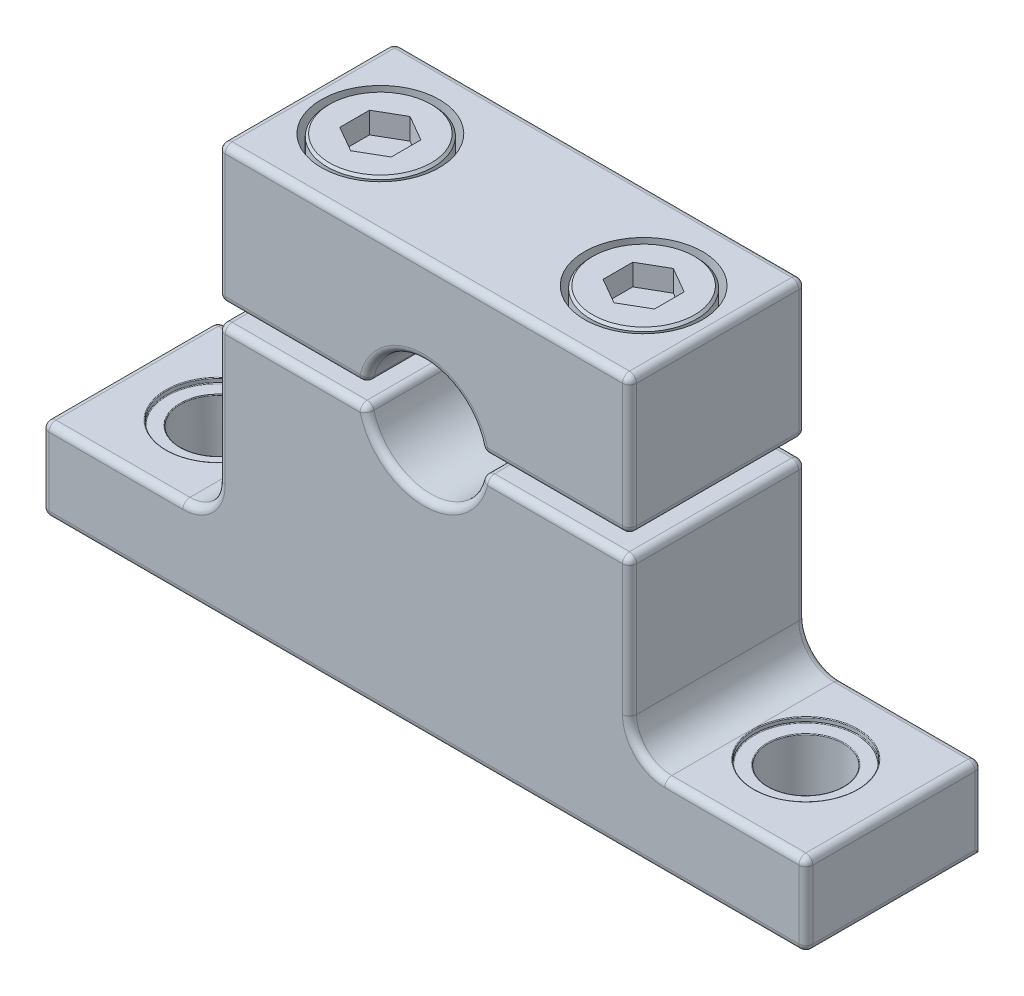
SolidWorks part; units mm, degrees
ref_plane "Front" through (0, 0, 0) normal (0, 0, 1) x (1, 0, 0)
ref_plane "Top" through (0, 0, 0) normal (0, 1, 0) x (1, 0, 0)
ref_plane "Right" through (0, 0, 0) normal (1, 0, 0) x (0, 0, -1)
sketch "Sketch1" plane through (0, 0, 0) normal (0, 0, 1) x (1, 0, 0)
  line L0 (0, 22.225) -> (0, 0) construction
  line L1 (-20.6375, 0) -> (20.6375, 0) construction
  line L2 (0, 0) -> (0, 14.2875) construction
  line L3 (-15.875, 0) -> (15.875, 0) construction
  line L4 (13.843, 0) -> (17.907, 0) construction
  line L5 (17.907, 0) -> (17.907, 1.27) construction
  line L6 (13.843, 0) -> (13.843, 1.27) construction
  line L7 (-13.843, 0) -> (-13.843, 1.27) construction
  line L8 (-17.907, 0) -> (-17.907, 1.27) construction
  line L9 (-13.843, 0) -> (-17.907, 0) construction
  line L10 (-11.1125, 14.2875) -> (11.1125, 14.2875) construction
  line L11 (-11.1125, 13.7795) -> (11.1125, 13.7795) construction
  line L12 (-11.1125, 14.7955) -> (11.1125, 14.7955) construction
  line L13 (13.462, 0) -> (13.462, 1.27) construction
  line L14 (18.288, 0) -> (18.288, 1.27) construction
  line L15 (-13.462, 0) -> (-13.462, 1.27) construction
  line L16 (-18.288, 0) -> (-18.288, 1.27) construction
  line L17 (-11.0713, 13.7795) -> (11.0713, 13.7795) construction
  line L18 (-11.0713, 14.7955) -> (11.0713, 14.7955) construction
  line L19 (-11.0713, 14.2875) -> (11.0713, 14.2875) construction
  line L20 (-20.6375, 0) -> (-20.6375, 4.445) construction
  line L21 (-20.6375, 4.445) -> (-11.1125, 4.445) construction
  line L22 (-11.1125, 13.7795) -> (-11.1125, 4.445) construction
  line L23 (-11.1125, 14.7955) -> (-11.1125, 22.225) construction
  line L24 (-11.1125, 22.225) -> (11.1125, 22.225) construction
  line L25 (20.6375, 0) -> (20.6375, 4.445) construction
  line L26 (20.6375, 4.445) -> (11.1125, 4.445) construction
  line L27 (11.1125, 13.7795) -> (11.1125, 4.445) construction
  line L28 (11.1125, 14.7955) -> (11.1125, 22.225) construction
  line L29 (0, 22.225) -> (0, 18.7198) construction
  line L30 (0.3175, 18.7198) -> (-0.3175, 18.7198) construction
  line L31 (11.1125, 4.445) -> (11.1125, 0) construction
  circle A0 centre (0, 14.2875) radius 3.175 construction
  arc A1 (-13.0175, 4.445) -> (-11.1125, 6.35) centre (-13.0175, 6.35) ccw construction
  arc A2 (13.0175, 4.445) -> (11.1125, 6.35) centre (13.0175, 6.35) cw construction
  point P5 (0, 0)
  point P9 (0, 14.2875)
  point P11 (0, 0)
  point P12 (15.875, 0)
  point P13 (-15.875, 0)
  point P16 (15.875, 0)
  point P37 (0, 13.7795)
  point P40 (0, 14.7955)
  point P60 (0, 18.7198)
  point P64 (15.875, 4.445)
  dimension "D1" = 1.27
  dimension "D8" = 4.445
  dimension "D12" = 0.635
  dimension "D10" = 1.905
  dimension "D11" = 1.905
  dimension "D9" = 4.7625
  dimension "D13" = 4.7625
  dimension "D3" = 0.508
  dimension "D4" = 0.381
  dimension "D5" = 0.381
  dimension "D6" = 0.381
  dimension "D7" = 0.381
sketch "Sketch3" plane through (0, 0, 0) normal (0, 0, 1) x (1, 0, 0)
  line L0 (-11.1125, 22.225) -> (11.1125, 22.225) construction
  line L1 (11.1125, 14.7955) -> (11.1125, 22.225) construction
  line L2 (-11.1125, 14.7955) -> (11.1125, 14.7955) construction
  line L3 (-11.1125, 14.7955) -> (-11.1125, 22.225) construction
  line L4 (-11.1125, 13.7795) -> (-11.1125, 4.445) construction
  line L5 (-20.6375, 4.445) -> (-11.1125, 4.445) construction
  line L6 (-20.6375, 0) -> (-20.6375, 4.445) construction
  line L7 (-20.6375, 0) -> (20.6375, 0) construction
  line L8 (20.6375, 0) -> (20.6375, 4.445) construction
  line L9 (20.6375, 4.445) -> (11.1125, 4.445) construction
  line L10 (11.1125, 13.7795) -> (11.1125, 4.445) construction
  line L11 (-11.1125, 13.7795) -> (11.1125, 13.7795) construction
  line L12 (-11.1125, 22.225) -> (11.1125, 22.225)
  line L13 (11.1125, 14.7955) -> (11.1125, 22.225)
  line L14 (-11.1125, 14.7955) -> (-3.1341, 14.7955)
  line L15 (-11.1125, 14.7955) -> (-11.1125, 22.225)
  line L16 (-11.1125, 13.7795) -> (-11.1125, 6.35)
  line L17 (-20.6375, 4.445) -> (-13.0175, 4.445)
  line L18 (-20.6375, 0) -> (-20.6375, 4.445)
  line L19 (-20.6375, 0) -> (20.6375, 0)
  line L20 (20.6375, 0) -> (20.6375, 4.445)
  line L21 (20.6375, 4.445) -> (13.0175, 4.445)
  line L22 (11.1125, 13.7795) -> (11.1125, 6.35)
  line L23 (-11.1125, 13.7795) -> (-3.1341, 13.7795)
  line L24 (3.1341, 14.7955) -> (11.1125, 14.7955)
  line L25 (3.1341, 13.7795) -> (11.1125, 13.7795)
  arc A0 (-13.0175, 4.445) -> (-11.1125, 6.35) centre (-13.0175, 6.35) ccw construction
  arc A1 (11.1125, 6.35) -> (13.0175, 4.445) centre (13.0175, 6.35) ccw construction
  circle A2 centre (0, 14.2875) radius 3.175 construction
  arc A3 (-13.0175, 4.445) -> (-11.1125, 6.35) centre (-13.0175, 6.35) ccw
  arc A4 (11.1125, 6.35) -> (13.0175, 4.445) centre (13.0175, 6.35) ccw
  arc A5 (3.1341, 14.7955) -> (-3.1341, 14.7955) centre (0, 14.2875) ccw
  arc A6 (-3.1341, 13.7795) -> (3.1341, 13.7795) centre (0, 14.2875) ccw
extrude "Boss-Extrude1" add sketch "Sketch3" against normal blind 9.525
sketch "Sketch4" plane through (0, 0, 0) normal (0, -1, 0) x (1, 0, 0)
  line L0 (-20.6375, 0) -> (-20.6375, -9.525) construction
  line L1 (-20.6375, 0) -> (-11.1125, 0) construction
  line L2 (-20.6375, -4.7625) -> (20.6375, -4.7625) construction
  line L3 (20.6375, -9.525) -> (20.6375, 0) construction
  line L4 (-15.875, 0) -> (-15.875, -9.525) construction
  line L5 (15.875, 0) -> (15.875, -9.525) construction
  line L6 (-20.6375, -9.525) -> (20.6375, -9.525) construction
  line L7 (0, 0) -> (0, -9.525) construction
  circle A0 centre (-15.875, -4.7625) radius 2.032
  circle A1 centre (15.875, -4.7625) radius 2.032
  point P7 (-20.6375, -4.7625)
  dimension "D1" = 4.064
extrude "Cut-Extrude1" cut sketch "Sketch4" against normal through all
sketch "Sketch6" plane through (0, 4.445, 0) normal (0, 1, 0) x (1, 0, 0)
  line L0 (0, 0) -> (0, 9.525) construction
  line L1 (-20.6375, 0) -> (20.6375, 0) construction
  line L2 (11.1125, 9.525) -> (-11.1125, 9.525) construction
  circle A1 centre (-15.875, 4.7625) radius 2.032 construction
  circle A2 centre (-15.875, 4.7625) radius 2.032
  circle A4 centre (-15.875, 4.7625) radius 2.413
  circle A5 centre (15.875, 4.7625) radius 2.413
  dimension "D1" = 0.381
sketch "Sketch7" plane through (0, 0, 0) normal (0, 0, 1) x (1, 0, 0)
  line L0 (-20.6375, 4.191) -> (20.6375, 4.191) construction
  line L1 (-11.1125, 13.7795) -> (-11.1125, 0) construction
  line L2 (-20.6375, 0) -> (20.6375, 0) construction
  line L3 (11.1125, 13.7795) -> (11.1125, 0) construction
  line L5 (-20.6375, 0) -> (-20.6375, 4.445) construction
  line L6 (-20.6375, 4.445) -> (-11.1125, 4.445) construction
  line L7 (20.6375, 0) -> (20.6375, 4.445) construction
  line L8 (-15.875, 4.445) -> (-15.875, 4.191) construction
  line L9 (15.875, 4.445) -> (15.875, 4.191) construction
  line L10 (20.6375, 4.445) -> (11.1125, 4.445) construction
  dimension "D1" = 0.254
sketch "Sketch8" plane through (0, 13.7795, 0) normal (0, 1, 0) x (1, 0, 0)
  line L0 (0, 0) -> (0, 9.525) construction
  line L1 (11.1125, 9.525) -> (-11.1125, 9.525) construction
  circle A0 centre (-15.875, 4.7625) radius 2.413 construction
  circle A1 centre (15.875, 4.7625) radius 2.413 construction
  circle A2 centre (-15.875, 4.7625) radius 2.413 construction
  circle A3 centre (15.875, 4.7625) radius 2.413 construction
  circle A4 centre (-15.875, 4.7625) radius 2.794
  circle A5 centre (15.875, 4.7625) radius 2.794
  dimension "D1" = 0.381
extrude "Cut-Extrude3" cut sketch "Sketch8" against normal up to vertex (9.5885 mm away) up to point (-15.875, 4.191, 0)
sketch "Sketch10" plane through (0, 22.225, 0) normal (0, 1, 0) x (1, 0, 0)
  line L0 (-11.1125, 9.525) -> (-11.1125, 0) construction
  line L1 (11.1125, 9.525) -> (11.1125, 0) construction
  line L2 (-11.1125, 9.525) -> (-11.1125, 0) construction
  line L3 (11.1125, 9.525) -> (11.1125, 0) construction
  line L4 (-9.9822, 9.525) -> (-9.9822, 0) construction
  line L5 (0, 0) -> (0, 9.525) construction
  line L6 (9.9822, 9.525) -> (9.9822, 0) construction
  circle A0 centre (-7.112, 4.7625) radius 1.7526 construction
  circle A1 centre (7.112, 4.7625) radius 2.0066
  circle A2 centre (-7.112, 4.7625) radius 2.0066
  circle A3 centre (7.112, 4.7625) radius 1.7526 construction
  circle A4 centre (-7.112, 4.7625) radius 2.8702 construction
  circle A5 centre (7.112, 4.7625) radius 2.8702 construction
extrude "Cut-Extrude4" cut sketch "Sketch10" against normal through all
ref_plane "Plane1" through (0, 0, -4.7625) normal (0, 0, 1) x (1, 0, 0)
sketch "Sketch12" plane through (0, 22.225, 0) normal (0, 1, 0) x (1, 0, 0)
  line L0 (0, 9.525) -> (0, 0) construction
  circle A0 centre (-7.112, 4.7625) radius 3.0607 construction
  circle A1 centre (7.112, 4.7625) radius 3.1877
  circle A2 centre (-7.112, 4.7625) radius 3.1877
  circle A3 centre (7.112, 4.7625) radius 3.0607 construction
  dimension "D2" = 6.3754
  dimension "D1" = 0.127
extrude "Cut-Extrude5" cut sketch "Sketch12" against normal blind 3.8862
sketch "Sketch13" plane through (0, 0, 0) normal (0, 1, 0) x (1, 0, 0)
  line L0 (-7.112, 9.525) -> (-7.112, 0) construction
  line L1 (11.1125, 9.525) -> (-11.1125, 9.525) construction
  line L2 (0, 9.525) -> (0, 0) construction
  line L3 (7.112, 9.525) -> (7.112, 0) construction
  circle A0 centre (-7.112, 4.7625) radius 2.0066 construction
  point P2 (-7.112, 4.7625)
  point P9 (-7.112, 9.525)
  point P10 (-7.112, 0)
  point P17 (7.112, 9.525)
  point P18 (7.112, 0)
sketch "Sketch15" plane through (0, 0, -4.7625) normal (0, 0, 1) x (1, 0, 0)
  line L0 (-7.112, 8.89) -> (-7.112, 22.225) construction
  line L1 (-7.112, 22.225) -> (-9.9822, 22.225) construction
  line L2 (-9.9822, 22.225) -> (-9.9822, 18.7198) construction
  line L3 (-9.9822, 18.7198) -> (-8.8646, 18.7198) construction
  line L4 (-8.8646, 18.7198) -> (-8.8646, 8.89) construction
  line L5 (-8.8646, 8.89) -> (-7.112, 8.89) construction
  line L8 (-11.1125, 22.225) -> (11.1125, 22.225) construction
  line L9 (-7.112, 8.89) -> (-7.112, 22.225)
  line L10 (-7.112, 22.225) -> (-9.9822, 22.225)
  line L11 (-9.9822, 22.225) -> (-9.9822, 18.7198)
  line L12 (-9.9822, 18.7198) -> (-8.8646, 18.7198)
  line L13 (-8.8646, 18.7198) -> (-8.8646, 8.89)
  line L14 (-8.8646, 8.89) -> (-7.112, 8.89)
  dimension "D2" = 2.8702
  dimension "D1" = 3.5052
  dimension "D3" = 1.7526
  dimension "Screw Length" = 13.335
revolve "Revolve1" add sketch "Sketch15" angle 360 about L9
chamfer "Chamfer1" distance 0.127 angle 45 1 edges at (-7.112, 22.225, -7.6327)
sketch "Sketch16" plane through (0, 22.225, 0) normal (0, 1, 0) x (1, 0, 0)
  line L0 (-7.112, 9.525) -> (-7.112, 0) construction
  line L1 (-7.112, 6.3665) -> (-8.5011, 5.5645)
  line L2 (-8.5011, 5.5645) -> (-8.5011, 3.9605)
  line L3 (-8.5011, 3.9605) -> (-7.112, 3.1585)
  line L4 (-7.112, 3.1585) -> (-5.7229, 3.9605)
  line L5 (-5.7229, 3.9605) -> (-5.7229, 5.5645)
  line L6 (-5.7229, 5.5645) -> (-7.112, 6.3665)
  circle A0 centre (-7.112, 4.7625) radius 1.3891 construction
  dimension "Hex Size" = 2.7781
extrude "Cut-Extrude6" cut sketch "Sketch16" against normal blind 1.1567
mirror "Mirror1" about plane through (0, 0, 0) normal (1, 0, 0) of bodies 121 119
fillet "Fillet1" radius 0.381 18 edges at (0, 22.225, -9.525) (-11.1125, 22.225, -4.7625) (-11.1125, 18.5102, -9.525) (-11.1125, 18.5102, 0) (11.1125, 18.5103, -9.525) (11.1125, 22.225, -4.7625) (11.1125, 18.5103, 0) (0, 22.225, 0) (11.1125, 14.7955, -4.7625) (7.1233, 14.7955, -9.525) (-7.1233, 14.7955, -9.525) (-11.1125, 14.7955, -4.7625) (-7.1233, 14.7955, 0) (7.1233, 14.7955, 0) (0, 17.4625, -9.525) (0, 17.4625, 0) (3.1341, 14.7955, -4.7625) (-3.1341, 14.7955, -4.7625)
fillet "Fillet2" radius 0.381 31 edges at (16.8275, 4.445, -9.525) (11.6705, 5.003, -9.525) (11.1125, 10.0648, 0) (11.6705, 5.003, 0) (-16.8275, 4.445, 0) (-11.6705, 5.003, 0) (-16.8275, 4.445, -9.525) (-11.6705, 5.003, -9.525) (11.1125, 10.0648, -9.525) (20.6375, 0, -4.7625) (20.6375, 2.2225, -9.525) (20.6375, 4.445, -4.7625) (16.8275, 4.445, 0) (20.6375, 2.2225, 0) (0, 0, 0) (-20.6375, 2.2225, -9.525) (-20.6375, 0, -4.7625) (-20.6375, 4.445, -4.7625) (-20.6375, 2.2225, 0) (-11.1125, 10.0648, 0) (-11.1125, 10.0648, -9.525) (11.1125, 13.7795, -4.7625) (-11.1125, 13.7795, -4.7625) (-7.1233, 13.7795, 0) (7.1233, 13.7795, 0) (7.1233, 13.7795, -9.525) (-7.1233, 13.7795, -9.525) (0, 11.1125, -9.525) (0, 11.1125, 0) (3.1341, 13.7795, -4.7625) (-3.1341, 13.7795, -4.7625)
fillet "Fillet3" radius 0.0381 6 edges at (-18.669, 4.191, -4.7625) (18.669, 4.191, -4.7625) (13.081, 4.445, -4.7625) (17.907, 4.191, -4.7625) (-18.669, 4.445, -4.7625) (-17.907, 4.191, -4.7625)
sketch "Sketch19" [suppressed] plane through (0, 0, 0) normal (0, 0, 1) x (1, 0, 0)
  line L0 (-0.7296, 32.258) -> (0.7296, 32.258)
  line L1 (0.7296, 31.242) -> (-0.7296, 31.242)
  arc A0 (-0.7296, 31.242) -> (0.7296, 31.242) centre (0, 31.75) ccw construction
  arc A1 (0.7296, 32.258) -> (-0.7296, 32.258) centre (0, 31.75) ccw construction
  arc A2 (-0.7296, 31.242) -> (0.7296, 31.242) centre (0, 31.75) ccw
  arc A3 (0.7296, 32.258) -> (-0.7296, 32.258) centre (0, 31.75) ccw
extrude "Boss-Extrude3" [suppressed] add sketch "Sketch19" against normal through all
fillet "Fillet5" [suppressed] radius 0.381
fillet "Fillet6" [suppressed] radius 0.381
ref_plane "Contact Plane 1" through (0, 0, -4.7625) normal (0, 0, -1) x (-1, 0, 0)
ref_plane "Contact Plane 2" through (0, 0, 0) normal (-1, 0, 0) x (0, 0, 1)
ref_plane "Contact Plane 3" through (0, 11.1125, 0) normal (0, 1, 0) x (1, 0, 0)
ref_plane "Contact Plane 4" through (0, 22.225, 0) normal (0, 1, 0) x (1, 0, 0)
ref_plane "Contact Plane 5" through (0, 0, 0) normal (0, -1, 0) x (-1, 0, 0)
ref_plane "Contact Plane 6" through (20.6375, 0, 0) normal (1, 0, 0) x (0, 0, -1)
ref_plane "Contact Plane 7" through (-20.6375, 0, 0) normal (-1, 0, 0) x (0, 0, 1)
ref_axis "Center Axis 1" through (0, 54.8037, -4.7625) along (0, -1, 0)
ref_axis "Center Axis 2" through (0, 11.1125, -33.3184) along (0, 0, 1)
ref_axis "Center Axis 3" through (69.4309, 11.1125, -4.7625) along (-1, 0, 0)
equation "\"D8@Sketch1\"=\"Oall Ht@Sketch1\"*.20"
equation "\"D1@Sketch4\"= \"HoldDia@Sketch1\""
equation "\"D1@Cut-Extrude5\"=\"HeadDp@Sketch1\"+.015"
equation "\"D1@Sketch15\"=\"HeadDp@Sketch1\""
equation "\"D3@Sketch15\"=\"ThrdDia@Sketch10\"*.5"
equation "\"D1@Cut-Extrude6\"= \"HeadDp@Sketch1\"*.33"
equation "\"D2@Sketch12\"=\"Head Dia@Sketch10\"+.025"
equation "\"D2@Sketch15\"=\"Head Dia@Sketch10\"*.50"
equation "\"D13@Sketch1\"=\"D9@Sketch1\""
